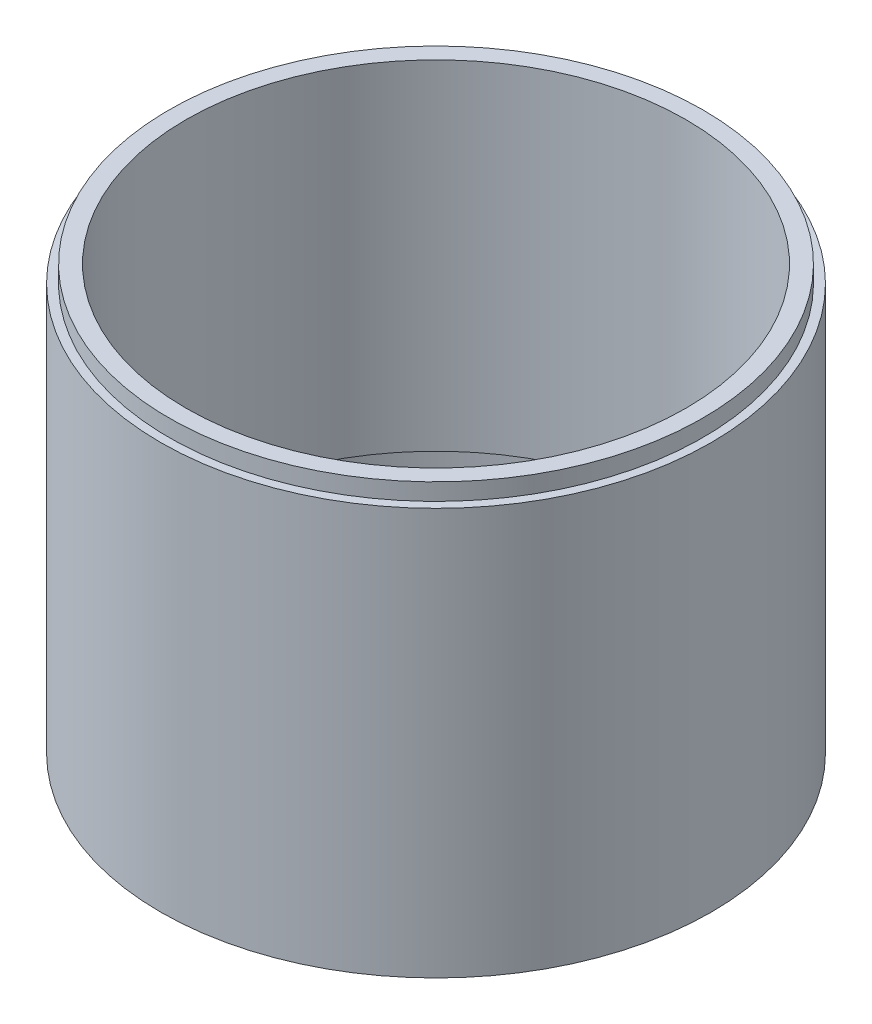
SolidWorks part; units mm, degrees
material "HYPALON"
ref_plane "Front Plane" through (0, 0, 0) normal (0, 0, 1) x (1, 0, 0)
ref_plane "Top Plane" through (0, 0, 0) normal (0, 1, 0) x (1, 0, 0)
ref_plane "Right Plane" through (0, 0, 0) normal (1, 0, 0) x (0, 0, -1)
sketch "Szkic1" plane through (0, 0, 0) normal (0, 0, 1) x (1, 0, 0)
  line L0 (0, 0) -> (-65, 0)
  line L1 (-65, 0) -> (-65, 20)
  line L2 (-62, 20) -> (-59, 20)
  line L3 (-59, 20) -> (-59, 100)
  line L4 (-62, 20) -> (-62, 0)
  line L5 (-59, 100) -> (-63, 100)
  line L7 (-65, 20) -> (-65, 96)
  line L8 (-65, 96) -> (-63, 96)
  line L9 (-63, 96) -> (-63, 100)
  line L13 (0, 0) -> (0, 22.4148)
  dimension "D1" = 65
  dimension "D2" = 20
  dimension "D3" = 6
  dimension "D4" = 100
  dimension "D5" = 3
  dimension "D7" = 2
  dimension "D8" = 4
revolve "Obrót1" add sketch "Szkic1" angle 360 about L13 region at (-62.1391, 53.7895, 0)
